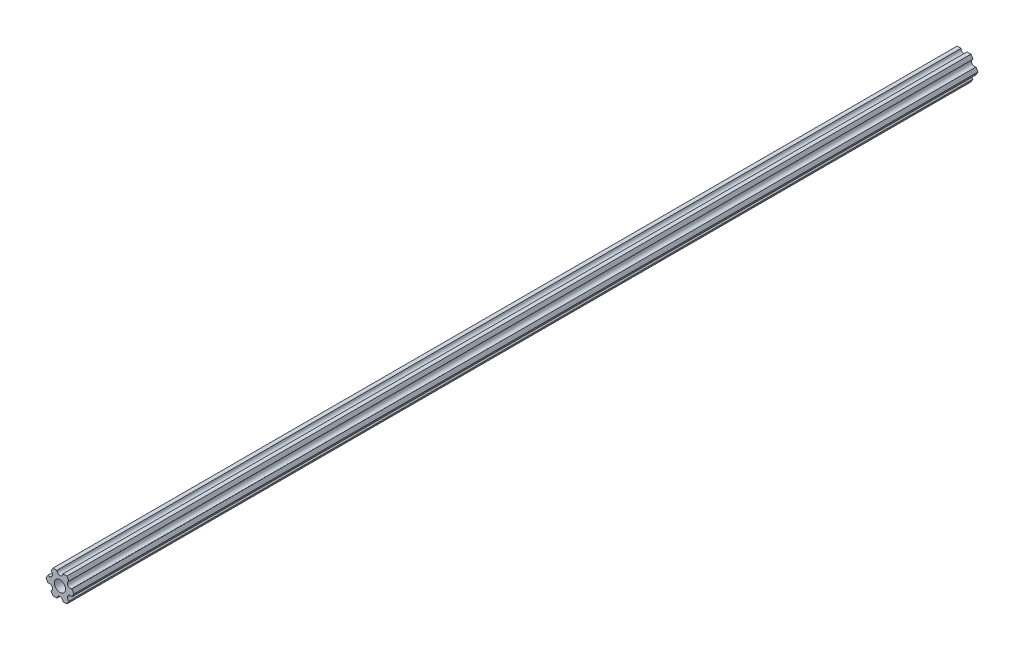
SolidWorks part; units mm, degrees
material "6061-T6 (SS)"
ref_plane "Front Plane" through (0, 0, 0) normal (0, 0, 1) x (1, 0, 0)
ref_plane "Top Plane" through (0, 0, 0) normal (0, 1, 0) x (1, 0, 0)
ref_plane "Right Plane" through (0, 0, 0) normal (1, 0, 0) x (0, 0, -1)
sketch "Sketch1" plane through (0, 0, 0) normal (0, 0, 1) x (1, 0, 0)
  line L0 (-4.7055, -4.5498) -> (-3.6662, -6.35)
  line L1 (-3.6662, -6.35) -> (-1.5875, -6.35)
  line L2 (1.5875, -6.35) -> (3.6662, -6.35)
  line L3 (3.6662, -6.35) -> (4.7055, -4.5498)
  line L4 (6.293, -1.8002) -> (7.3323, 0)
  line L5 (7.3323, 0) -> (6.293, 1.8002)
  line L6 (4.7055, 4.5498) -> (3.6662, 6.35)
  line L7 (3.6662, 6.35) -> (1.5875, 6.35)
  line L8 (-1.5875, 6.35) -> (-3.6662, 6.35)
  line L9 (-3.6662, 6.35) -> (-4.7055, 4.5498)
  line L10 (-6.293, 1.8002) -> (-7.3323, 0)
  line L11 (-7.3323, 0) -> (-6.293, -1.8002)
  circle A0 centre (0, 0) radius 2.9337
  arc A1 (-6.293, -1.8002) -> (-4.7055, -4.5498) centre (-5.4993, -3.175) cw
  arc A2 (-1.5875, -6.35) -> (1.5875, -6.35) centre (0, -6.35) cw
  arc A3 (4.7055, -4.5498) -> (6.293, -1.8002) centre (5.4993, -3.175) cw
  arc A4 (6.293, 1.8002) -> (4.7055, 4.5498) centre (5.4993, 3.175) cw
  arc A5 (1.5875, 6.35) -> (-1.5875, 6.35) centre (0, 6.35) cw
  arc A6 (-4.7055, 4.5498) -> (-6.293, 1.8002) centre (-5.4993, 3.175) cw
extrude "Boss-Extrude1" add sketch "Sketch1" against normal blind 476.25
